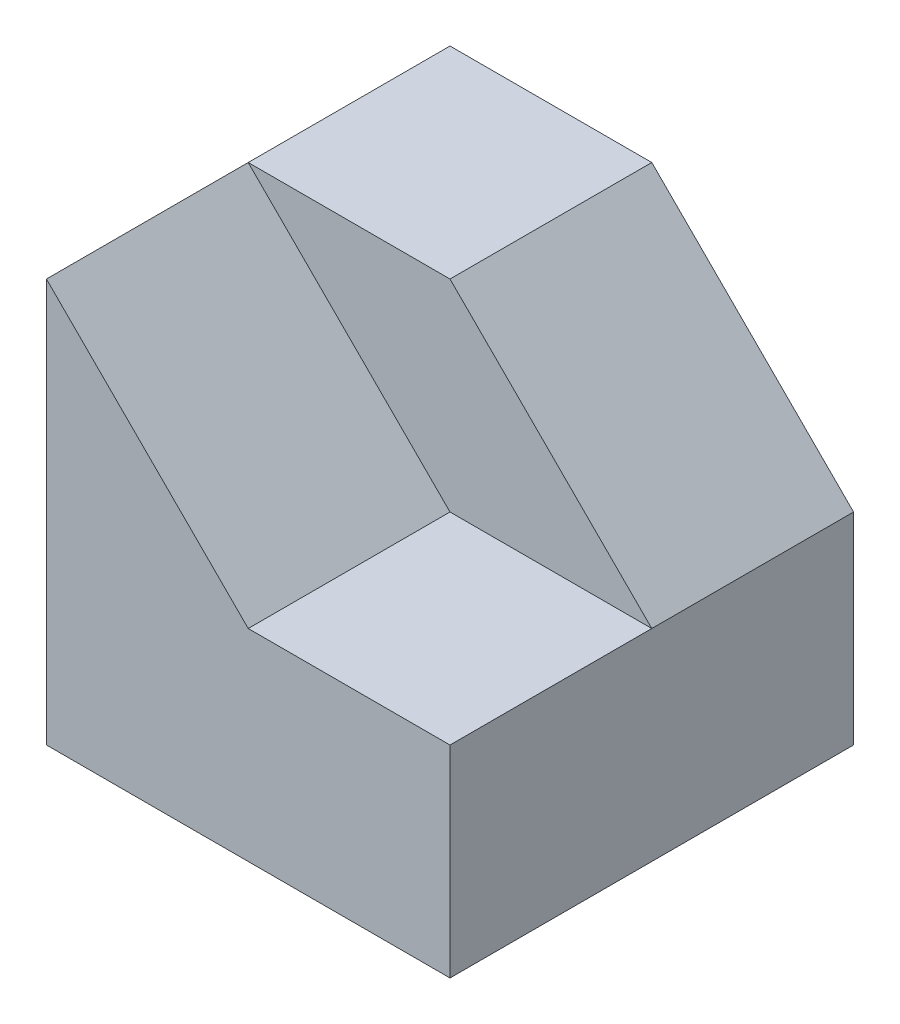
SolidWorks part; units mm, degrees
ref_plane "Alzado" through (0, 0, 0) normal (0, 0, 1) x (1, 0, 0)
ref_plane "Planta" through (0, 0, 0) normal (0, 1, 0) x (1, 0, 0)
ref_plane "Vista lateral" through (0, 0, 0) normal (1, 0, 0) x (0, 0, -1)
sketch "Croquis1" plane through (0, 0, 0) normal (0, 1, 0) x (1, 0, 0)
  line L1 (30, 30) -> (-30, 30)
  line L2 (30, 30) -> (30, -30)
  line L3 (30, -30) -> (-30, -30)
  line L4 (-30, 30) -> (-30, -30)
  line L5 (30, 30) -> (-30, -30) construction
  line L6 (30, -30) -> (-30, 30) construction
  point P0 (0, 0)
  dimension "D1" = 60
  dimension "D2" = 60
extrude "Saliente-Extruir1" add sketch "Croquis1" along normal blind 30 contours L2 L1 L4 L3
sketch "Croquis2" plane through (0, 30, 0) normal (0, 1, 0) x (1, 0, 0)
  line L0 (0, -30) -> (0, 0)
  line L1 (0, 0) -> (30, 0)
  line L4 (-30, -30) -> (30, -30)
  line L5 (30, -30) -> (30, 30)
  line L6 (30, 30) -> (-30, 30)
  line L7 (-30, 30) -> (-30, -30)
  line L8 (-30, -30) -> (0, -30)
  line L9 (30, 0) -> (30, 30)
  line L10 (30, 30) -> (-30, 30)
  line L11 (-30, 30) -> (-30, -30)
  dimension "D2" = 30
  dimension "D3" = 30
  dimension "D1" = 0
extrude "Saliente-Extruir2" add sketch "Croquis2" along normal blind 30 contours L8 L0 L1 L9 L10 L11
chamfer "Chaflán1" distance 30 1 edges at (0, 60, 15)
chamfer "Chaflán2" distance 30 angle 45 1 edges at (30, 60, -15)
